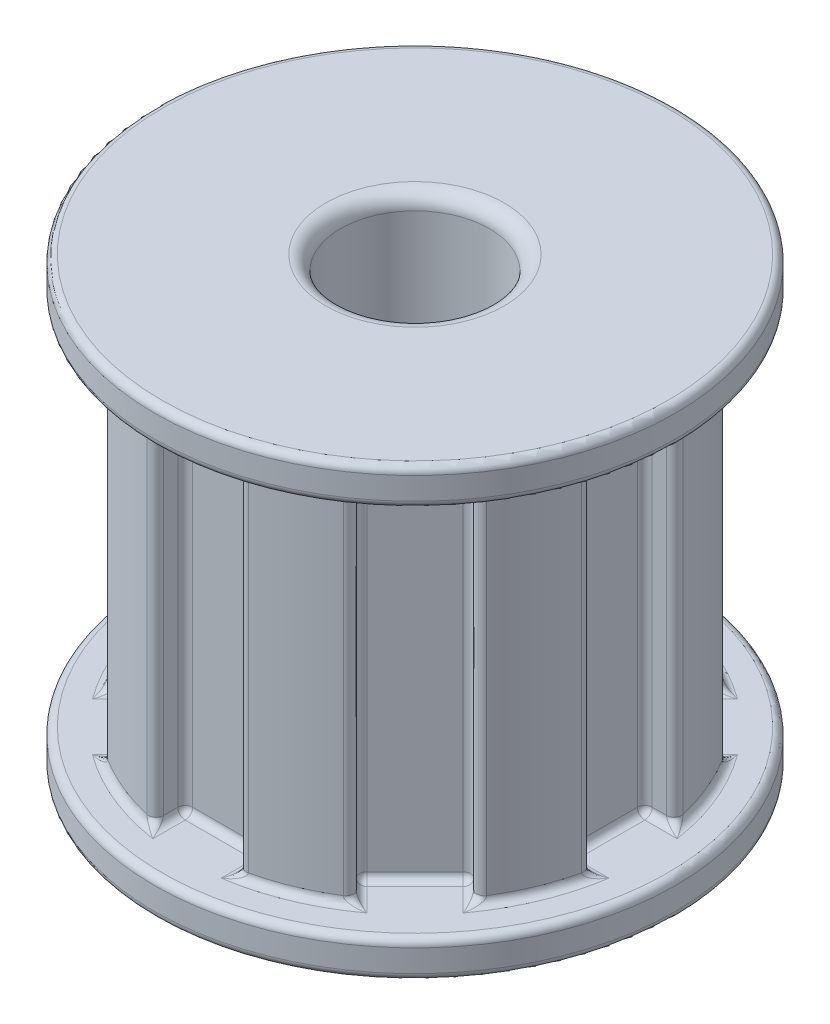
SolidWorks part; units mm, degrees
ref_plane "Front Plane" through (0, 0, 0) normal (0, 0, 1) x (1, 0, 0)
ref_plane "Top Plane" through (0, 0, 0) normal (0, 1, 0) x (1, 0, 0)
ref_plane "Right Plane" through (0, 0, 0) normal (1, 0, 0) x (0, 0, -1)
sketch "Sketch1" plane through (0, 0, 0) normal (0, 1, 0) x (1, 0, 0)
  line L28 (0, 0) -> (0, 30) construction
  line L33 (16.8954, 24.79) -> (13.9494, 21.8439)
  line L35 (-5.5823, 29.4761) -> (-5.5823, 25.3097)
  line L36 (-5.5823, 25.3097) -> (5.5823, 25.3097)
  line L37 (5.5823, 29.4761) -> (5.5823, 25.3097)
  line L38 (0, 25.3097) -> (0, 32.5) construction
  line L39 (-4, 30) -> (4, 30) construction
  line L40 (13.9494, 21.8439) -> (21.8439, 13.9494)
  line L41 (24.79, 16.8954) -> (21.8439, 13.9494)
  line L42 (29.4761, 5.5823) -> (25.3097, 5.5823)
  line L43 (25.3097, 5.5823) -> (25.3097, -5.5823)
  line L44 (29.4761, -5.5823) -> (25.3097, -5.5823)
  line L45 (24.79, -16.8954) -> (21.8439, -13.9494)
  line L46 (21.8439, -13.9494) -> (13.9494, -21.8439)
  line L47 (16.8954, -24.79) -> (13.9494, -21.8439)
  line L48 (5.5823, -29.4761) -> (5.5823, -25.3097)
  line L49 (5.5823, -25.3097) -> (-5.5823, -25.3097)
  line L50 (-5.5823, -29.4761) -> (-5.5823, -25.3097)
  line L51 (-16.8954, -24.79) -> (-13.9494, -21.8439)
  line L52 (-13.9494, -21.8439) -> (-21.8439, -13.9494)
  line L53 (-24.79, -16.8954) -> (-21.8439, -13.9494)
  line L54 (-29.4761, -5.5823) -> (-25.3097, -5.5823)
  line L55 (-25.3097, -5.5823) -> (-25.3097, 5.5823)
  line L56 (-29.4761, 5.5823) -> (-25.3097, 5.5823)
  line L57 (-24.79, 16.8954) -> (-21.8439, 13.9494)
  line L58 (-21.8439, 13.9494) -> (-13.9494, 21.8439)
  line L59 (-16.8954, 24.79) -> (-13.9494, 21.8439)
  arc A1 (-5.5823, 29.4761) -> (-16.8954, 24.79) centre (0, 0) ccw
  arc A2 (16.8954, 24.79) -> (5.5823, 29.4761) centre (0, 0) ccw
  arc A3 (29.4761, 5.5823) -> (24.79, 16.8954) centre (0, 0) ccw
  arc A4 (24.79, -16.8954) -> (29.4761, -5.5823) centre (0, 0) ccw
  arc A5 (5.5823, -29.4761) -> (16.8954, -24.79) centre (0, 0) ccw
  arc A6 (-16.8954, -24.79) -> (-5.5823, -29.4761) centre (0, 0) ccw
  arc A7 (-29.4761, -5.5823) -> (-24.79, -16.8954) centre (0, 0) ccw
  arc A8 (-24.79, 16.8954) -> (-29.4761, 5.5823) centre (0, 0) ccw
  circle A9 centre (0, 0) radius 10
  point P1 (0, 30)
  point P10 (0, 0)
  point P43 (0, 0)
  dimension "D1" = 60
  dimension "D2" = 30
  dimension "D4" = 20
  dimension "D3" = 8
extrude "Boss-Extrude1" add sketch "Sketch1" along normal blind 60
sketch "Sketch2" plane through (0, 60, 0) normal (0, 1, 0) x (1, 0, 0)
  circle A0 centre (0, 0) radius 35
  point P2 (0, 0)
  dimension "D1" = 70
extrude "Boss-Extrude2" add sketch "Sketch2" against normal blind 5
ref_plane "Plane1" through (0, 30, 0) normal (0, 1, 0) x (1, 0, 0)
mirror "Mirror1" about plane through (0, 30, 0) normal (0, 1, 0) of "Boss-Extrude2"
sketch "Sketch3" plane through (0, 60, 0) normal (0, 1, 0) x (1, 0, 0)
  circle A0 centre (0, 0) radius 10
  point P2 (0, 0)
  dimension "D1" = 20
extrude "Cut-Extrude1" cut sketch "Sketch3" against normal through all
fillet "Fillet1" radius 2 2 edges at (0, 60, 10) (0, 0, 10)
fillet "Fillet2" radius 1 2 edges at (0, 55, 35) (0, 60, 35)
fillet "Fillet3" radius 1 34 edges at (0, 5, 35) (-5.5823, 5, -27.3929) (-11.4805, 5, -27.7164) (-15.4224, 5, -23.317) (-17.8966, 5, -17.8966) (-23.317, 5, -15.4224) (-27.7164, 5, -11.4805) (-27.3929, 5, -5.5823) (-25.3097, 5, 0) (-27.3929, 5, 5.5823) (-27.7164, 5, 11.4805) (-23.317, 5, 15.4224) (-17.8966, 5, 17.8966) (-15.4224, 5, 23.317) (-11.4805, 5, 27.7164) (-5.5823, 5, 27.3929) (0, 5, 25.3097) (5.5823, 5, 27.3929) (11.4805, 5, 27.7164) (15.4224, 5, 23.317) (17.8966, 5, 17.8966) (23.317, 5, 15.4224) (27.7164, 5, 11.4805) (27.3929, 5, 5.5823) (25.3097, 5, 0) (27.3929, 5, -5.5823) (27.7164, 5, -11.4805) (23.317, 5, -15.4224) (17.8966, 5, -17.8966) (15.4224, 5, -23.317) (11.4805, 5, -27.7164) (5.5823, 5, -27.3929) (0, 5, -25.3097) (0, 0, 35)
fillet "Fillet4" radius 1 40 edges at (-21.8439, 5.2929, -14.3636) (-14.3636, 5.2929, -21.8439) (-5.2894, 5.2929, -25.6026) (5.2894, 5.2929, -25.6026) (14.3636, 5.2929, -21.8439) (21.8439, 5.2929, -14.3636) (25.6026, 5.2929, -5.2894) (25.6026, 5.2929, 5.2894) (21.8439, 5.2929, 14.3636) (14.3636, 5.2929, 21.8439) (5.2894, 5.2929, 25.6026) (-5.2894, 5.2929, 25.6026) (-14.3636, 5.2929, 21.8439) (-21.8439, 5.2929, 14.3636) (-25.6026, 5.2929, 5.2894) (-25.6026, 5.2929, -5.2894) (-17.8966, 55, -17.8966) (-21.8439, 30.5, -13.9494) (-13.9494, 30.5, -21.8439) (0, 55, -25.3097) (-5.5823, 30.5, -25.3097) (5.5823, 30.5, -25.3097) (17.8966, 55, -17.8966) (13.9494, 30.5, -21.8439) (21.8439, 30.5, -13.9494) (25.3097, 55, 0) (25.3097, 30.5, -5.5823) (25.3097, 30.5, 5.5823) (17.8966, 55, 17.8966) (21.8439, 30.5, 13.9494) (13.9494, 30.5, 21.8439) (0, 55, 25.3097) (5.5823, 30.5, 25.3097) (-5.5823, 30.5, 25.3097) (-17.8966, 55, 17.8966) (-13.9494, 30.5, 21.8439) (-21.8439, 30.5, 13.9494) (-25.3097, 55, 0) (-25.3097, 30.5, 5.5823) (-25.3097, 30.5, -5.5823)
fillet "Fillet5" radius 1 72 edges at (-25.6026, 54.7071, 5.2894) (-21.8439, 54.7071, 14.3636) (-21.8439, 54.7071, -14.3636) (-25.6026, 54.7071, -5.2894) (-5.2894, 54.7071, -25.6026) (-14.3636, 54.7071, -21.8439) (14.3636, 54.7071, -21.8439) (5.2894, 54.7071, -25.6026) (25.6026, 54.7071, -5.2894) (21.8439, 54.7071, -14.3636) (21.8439, 54.7071, 14.3636) (25.6026, 54.7071, 5.2894) (5.2894, 54.7071, 25.6026) (14.3636, 54.7071, 21.8439) (-14.3636, 54.7071, 21.8439) (-5.2894, 54.7071, 25.6026) (-27.8929, 55, 5.5823) (-23.6705, 55, 15.7759) (-23.6705, 55, -15.7759) (-27.8929, 55, -5.5823) (-5.5823, 55, -27.8929) (-15.7759, 55, -23.6705) (15.7759, 55, -23.6705) (5.5823, 55, -27.8929) (27.8929, 55, -5.5823) (23.6705, 55, -15.7759) (23.6705, 55, 15.7759) (27.8929, 55, 5.5823) (5.5823, 55, 27.8929) (15.7759, 55, 23.6705) (-15.7759, 55, 23.6705) (-5.5823, 55, 27.8929) (-24.8063, 5.5381, 17.0716) (-29.6122, 5.5381, 5.4693) (-29.6122, 5.5381, -5.4693) (-24.8063, 5.5381, -17.0716) (-17.0716, 5.5381, -24.8063) (-5.4693, 5.5381, -29.6122) (5.4693, 5.5381, -29.6122) (17.0716, 5.5381, -24.8063) (24.8063, 5.5381, -17.0716) (29.6122, 5.5381, -5.4693) (29.6122, 5.5381, 5.4693) (24.8063, 5.5381, 17.0716) (17.0716, 5.5381, 24.8063) (5.4693, 5.5381, 29.6122) (-5.4693, 5.5381, 29.6122) (-17.0716, 5.5381, 24.8063) (-27.7164, 55, 11.4805) (-24.79, 30.5, 16.8954) (-29.4761, 30.5, 5.5823) (-27.7164, 55, -11.4805) (-29.4761, 30.5, -5.5823) (-24.79, 30.5, -16.8954) (-11.4805, 55, -27.7164) (-16.8954, 30.5, -24.79) (-5.5823, 30.5, -29.4761) (11.4805, 55, -27.7164) (5.5823, 30.5, -29.4761) (16.8954, 30.5, -24.79) (27.7164, 55, -11.4805) (24.79, 30.5, -16.8954) (29.4761, 30.5, -5.5823) (27.7164, 55, 11.4805) (29.4761, 30.5, 5.5823) (24.79, 30.5, 16.8954) (11.4805, 55, 27.7164) (16.8954, 30.5, 24.79) (5.5823, 30.5, 29.4761) (-11.4805, 55, 27.7164) (-5.5823, 30.5, 29.4761) (-16.8954, 30.5, 24.79)
